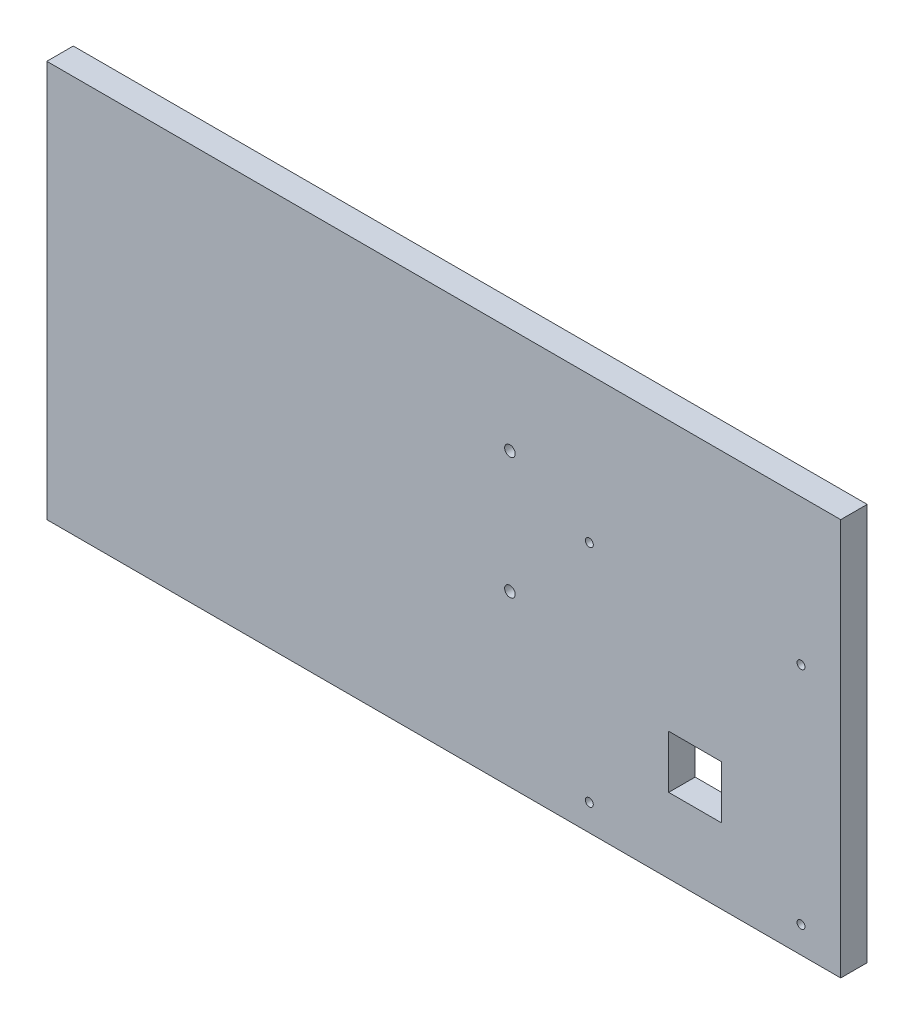
SolidWorks part; units mm, degrees
material "Faia"
ref_plane "Plano frontal" through (0, 0, 0) normal (0, 0, 1) x (1, 0, 0)
ref_plane "Plano superior" through (0, 0, 0) normal (0, 1, 0) x (1, 0, 0)
ref_plane "Plano direito" through (0, 0, 0) normal (1, 0, 0) x (0, 0, -1)
sketch "Esboço1" plane through (0, 0, 0) normal (0, 0, 1) x (1, 0, 0)
  line L0 (150, 0) -> (-150, 0) construction
  line L1 (-150, 75) -> (150, 75)
  line L2 (-150, 75) -> (-150, -75)
  line L3 (-150, -75) -> (150, -75)
  line L4 (150, 75) -> (150, -75)
  line L5 (-150, 75) -> (150, -75) construction
  line L6 (-150, -75) -> (150, 75) construction
  line L7 (70, 0) -> (-230, 0) construction
  line L8 (25, -11) -> (25, 35) construction
  line L9 (55, 20) -> (55, -65) construction
  line L10 (135, 20) -> (55, 20) construction
  line L11 (55, -65) -> (135, -65) construction
  line L13 (85, -26.75) -> (105, -26.75)
  line L14 (85, -26.75) -> (85, -46.75)
  line L15 (85, -46.75) -> (105, -46.75)
  line L16 (105, -26.75) -> (105, -46.75)
  line L17 (85, -26.75) -> (105, -46.75) construction
  line L18 (85, -46.75) -> (105, -26.75) construction
  circle A0 centre (135, 20) radius 1.5
  circle A1 centre (135, -65) radius 1.5
  circle A2 centre (55, -65) radius 1.5
  circle A3 centre (55, 20) radius 1.5
  circle A4 centre (25, 35) radius 2
  circle A5 centre (25, -11) radius 2
  point P0 (0, 0)
  point P21 (5, 0)
  point P23 (95, -36.75)
  point P28 (95, -65)
  dimension "D5" = 3
  dimension "D8" = 4
  dimension "D1" = 300
  dimension "D2" = 150
  dimension "D3" = 15
  dimension "D4" = 85
  dimension "D7" = 80
  dimension "D9" = 46
  dimension "D10" = 125
  dimension "D11" = 40
  dimension "D12" = 10
  dimension "D13" = 20
  dimension "D14" = 20
  dimension "D15" = 28.25
  dimension "D6" = 2
extrude "Ressalto-extrusão1" add sketch "Esboço1" along normal blind 10 contours L4 L1 L2 L3 A3 A1 A0 A2 region at (-0.9274, 0.3375, 0)
